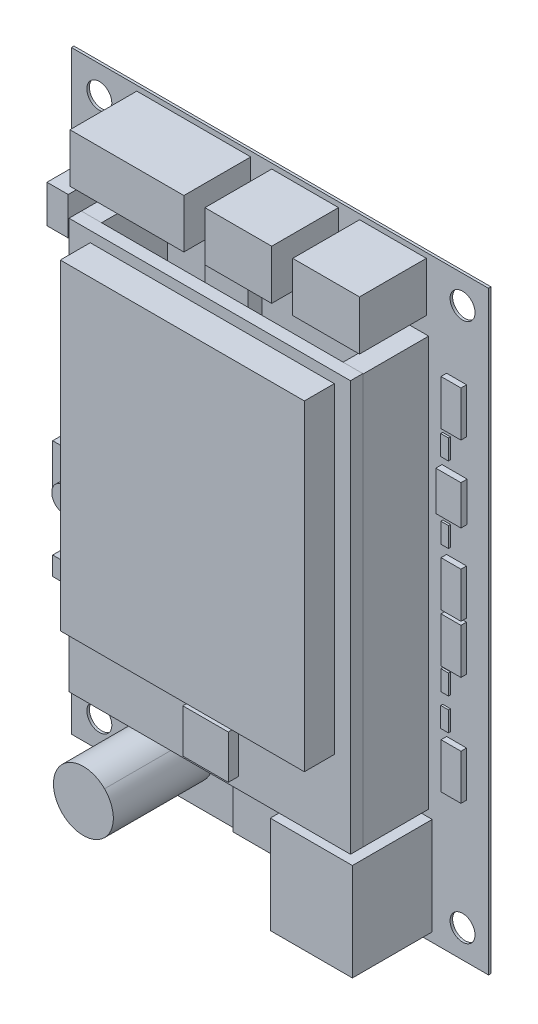
SolidWorks part; units mm, degrees
ref_plane "Front Plane" through (0, 0, 0) normal (0, 0, 1) x (1, 0, 0)
ref_plane "Top Plane" through (0, 0, 0) normal (0, 1, 0) x (1, 0, 0)
ref_plane "Right Plane" through (0, 0, 0) normal (1, 0, 0) x (0, 0, -1)
sketch "Sketch1" plane through (0, 0, 0) normal (0, 0, 1) x (1, 0, 0)
  line L0 (0, 0) -> (53.086, 0)
  line L1 (53.086, 0) -> (53.086, 75.692)
  line L2 (53.086, 75.692) -> (0, 75.692)
  line L3 (0, 75.692) -> (0, 0)
extrude "BOARD" add sketch "Sketch1" along normal blind 0.3226 separate body
ref_plane "Plane1" through (0, 0, 0.3226) normal (0, 0, 1) x (1, 0, 0)
sketch "Sketch3" plane through (0, 0, 0.3226) normal (0, 0, 1) x (1, 0, 0)
  line L0 (2.8301, 26.5189) -> (2.8301, 16.3187)
  line L1 (2.8301, 16.3187) -> (7.3299, 16.3187)
  line L2 (7.3299, 16.3187) -> (7.3299, 26.5189)
  line L3 (7.3299, 26.5189) -> (2.8301, 26.5189)
extrude "OS_SPDT-1" add sketch "Sketch3" along normal blind 3.9602 separate body
sketch "Sketch4" plane through (0, 0, 0.3226) normal (0, 0, 1) x (1, 0, 0)
  line L0 (19.6122, 6.096) -> (14.224, 11.4842)
  line L1 (14.224, 11.4842) -> (8.8358, 6.096)
  line L2 (8.8358, 6.096) -> (14.224, 0.7078)
  line L3 (14.224, 0.7078) -> (19.6122, 6.096)
extrude "SMA-50-TH-1" add sketch "Sketch4" along normal blind 12.7 separate body
sketch "Sketch5" plane through (0, 0, 0.3226) normal (0, 0, 1) x (1, 0, 0)
  line L0 (17.2989, 10.6759) -> (21.3091, 10.6759)
  line L1 (21.3091, 10.6759) -> (21.3091, 14.4031)
  line L2 (21.3091, 14.4031) -> (17.2989, 14.4031)
  line L3 (17.2989, 14.4031) -> (17.2989, 10.6759)
extrude "U_FL-1" add sketch "Sketch5" along normal blind 1.27 separate body
sketch "Sketch6" plane through (0, 0, 0.3226) normal (0, 0, 1) x (1, 0, 0)
  line L0 (33.798, 17.194) -> (23.098, 17.194)
  line L1 (23.098, 17.194) -> (23.098, 2.05)
  line L2 (23.098, 2.05) -> (33.798, 2.05)
  line L3 (33.798, 2.05) -> (33.798, 17.194)
extrude "DDPAK-1" add sketch "Sketch6" along normal blind 2.54 separate body
sketch "Sketch7" plane through (0, 0, 0.3226) normal (0, 0, 1) x (1, 0, 0)
  line L0 (24.2301, 55.4919) -> (24.2301, 62.8721)
  line L1 (24.2301, 62.8721) -> (18.7706, 62.8721)
  line L2 (18.7706, 62.8721) -> (18.7706, 55.4919)
  line L3 (18.7706, 55.4919) -> (24.2301, 55.4919)
extrude "SOIC8-1" add sketch "Sketch7" along normal blind 1.7526 separate body
sketch "Sketch8" plane through (0, 0, 0.3226) normal (0, 0, 1) x (1, 0, 0)
  line L0 (8.654, 23.876) -> (8.654, 21.336)
  line L1 (8.654, 21.336) -> (9.6241, 21.336)
  line L2 (9.6241, 21.336) -> (9.6241, 23.876)
  line L3 (9.6241, 23.876) -> (8.654, 23.876)
extrude "0603-R-1" add sketch "Sketch8" along normal blind 0.254 separate body
sketch "Sketch9" plane through (0, 0, 0.3226) normal (0, 0, 1) x (1, 0, 0)
  line L0 (47.752, 23.622) -> (47.752, 17.874)
  line L1 (47.752, 17.874) -> (50.292, 17.874)
  line L2 (50.292, 17.874) -> (50.292, 23.622)
  line L3 (50.292, 23.622) -> (47.752, 23.622)
extrude "0805_POL-1" add sketch "Sketch9" along normal blind 0.7112 separate body
sketch "Sketch10" plane through (0, 0, 0.3226) normal (0, 0, 1) x (1, 0, 0)
  line L0 (47.262, 26.924) -> (47.262, 24.384)
  line L1 (47.262, 24.384) -> (48.2321, 24.384)
  line L2 (48.2321, 24.384) -> (48.2321, 26.924)
  line L3 (48.2321, 26.924) -> (47.262, 26.924)
extrude "0603-R-2" add sketch "Sketch10" along normal blind 0.254 separate body
sketch "Sketch11" plane through (0, 0, 0.3226) normal (0, 0, 1) x (1, 0, 0)
  line L0 (48.242, 28.448) -> (48.242, 30.988)
  line L1 (48.242, 30.988) -> (47.2719, 30.988)
  line L2 (47.2719, 30.988) -> (47.2719, 28.448)
  line L3 (47.2719, 28.448) -> (48.242, 28.448)
extrude "0603-R-3" add sketch "Sketch11" along normal blind 0.254 separate body
sketch "Sketch12" plane through (0, 0, 0.3226) normal (0, 0, 1) x (1, 0, 0)
  line L0 (50.292, 31.75) -> (50.292, 37.498)
  line L1 (50.292, 37.498) -> (47.752, 37.498)
  line L2 (47.752, 37.498) -> (47.752, 31.75)
  line L3 (47.752, 31.75) -> (50.292, 31.75)
extrude "0805_POL-2" add sketch "Sketch12" along normal blind 0.7112 separate body
sketch "Sketch13" plane through (0, 0, 0.3226) normal (0, 0, 1) x (1, 0, 0)
  line L0 (30.48, 20.556) -> (27.94, 20.556)
  line L1 (27.94, 20.556) -> (27.94, 19.5859)
  line L2 (27.94, 19.5859) -> (30.48, 19.5859)
  line L3 (30.48, 19.5859) -> (30.48, 20.556)
extrude "0603-R-4" add sketch "Sketch13" along normal blind 0.254 separate body
sketch "Sketch14" plane through (0, 0, 0.3226) normal (0, 0, 1) x (1, 0, 0)
  line L0 (50.3679, 48.2999) -> (50.3679, 53.3001)
  line L1 (50.3679, 53.3001) -> (47.1681, 53.3001)
  line L2 (47.1681, 53.3001) -> (47.1681, 48.2999)
  line L3 (47.1681, 48.2999) -> (50.3679, 48.2999)
extrude "SOT505-2-1" add sketch "Sketch14" along normal blind 0.7879 separate body
sketch "Sketch15" plane through (0, 0, 0.3226) normal (0, 0, 1) x (1, 0, 0)
  line L0 (32.7025, 22.987) -> (27.7495, 22.987)
  line L1 (27.7495, 22.987) -> (27.7495, 21.209)
  line L2 (27.7495, 21.209) -> (32.7025, 21.209)
  line L3 (32.7025, 21.209) -> (32.7025, 22.987)
extrude "1206-R-1" add sketch "Sketch15" along normal blind 0.635 separate body
sketch "Sketch16" plane through (0, 0, 0.3226) normal (0, 0, 1) x (1, 0, 0)
  line L0 (16.238, 16.764) -> (16.238, 19.304)
  line L1 (16.238, 19.304) -> (15.2679, 19.304)
  line L2 (15.2679, 19.304) -> (15.2679, 16.764)
  line L3 (15.2679, 16.764) -> (16.238, 16.764)
extrude "0603-R-5" add sketch "Sketch16" along normal blind 0.254 separate body
sketch "Sketch17" plane through (0, 0, 0.3226) normal (0, 0, 1) x (1, 0, 0)
  line L0 (26.416, 18.052) -> (28.956, 18.052)
  line L1 (28.956, 18.052) -> (28.956, 19.0221)
  line L2 (28.956, 19.0221) -> (26.416, 19.0221)
  line L3 (26.416, 19.0221) -> (26.416, 18.052)
extrude "0603-R-6" add sketch "Sketch17" along normal blind 0.254 separate body
sketch "Sketch18" plane through (0, 0, 0.3226) normal (0, 0, 1) x (1, 0, 0)
  line L0 (47.262, 56.896) -> (47.262, 54.356)
  line L1 (47.262, 54.356) -> (48.2321, 54.356)
  line L2 (48.2321, 54.356) -> (48.2321, 56.896)
  line L3 (48.2321, 56.896) -> (47.262, 56.896)
extrude "0603-R-7" add sketch "Sketch18" along normal blind 0.254 separate body
sketch "Sketch19" plane through (0, 0, 0.3226) normal (0, 0, 1) x (1, 0, 0)
  line L0 (48.242, 44.704) -> (48.242, 47.244)
  line L1 (48.242, 47.244) -> (47.2719, 47.244)
  line L2 (47.2719, 47.244) -> (47.2719, 44.704)
  line L3 (47.2719, 44.704) -> (48.242, 44.704)
extrude "0603-R-8" add sketch "Sketch19" along normal blind 0.254 separate body
sketch "Sketch20" plane through (0, 0, 0.3226) normal (0, 0, 1) x (1, 0, 0)
  line L0 (24.0665, 54.229) -> (19.1135, 54.229)
  line L1 (19.1135, 54.229) -> (19.1135, 52.451)
  line L2 (19.1135, 52.451) -> (24.0665, 52.451)
  line L3 (24.0665, 52.451) -> (24.0665, 54.229)
extrude "1206-R-2" add sketch "Sketch20" along normal blind 0.635 separate body
sketch "Sketch21" plane through (0, 0, 0.3226) normal (0, 0, 1) x (1, 0, 0)
  line L0 (47.752, 43.688) -> (47.752, 37.94)
  line L1 (47.752, 37.94) -> (50.292, 37.94)
  line L2 (50.292, 37.94) -> (50.292, 43.688)
  line L3 (50.292, 43.688) -> (47.752, 43.688)
extrude "0805_POL-3" add sketch "Sketch21" along normal blind 0.7112 separate body
sketch "Sketch22" plane through (0, 0, 0.3226) normal (0, 0, 1) x (1, 0, 0)
  line L0 (50.292, 57.912) -> (50.292, 63.66)
  line L1 (50.292, 63.66) -> (47.752, 63.66)
  line L2 (47.752, 63.66) -> (47.752, 57.912)
  line L3 (47.752, 57.912) -> (50.292, 57.912)
extrude "0805_POL-4" add sketch "Sketch22" along normal blind 0.7112 separate body
sketch "Sketch23" plane through (0, 0, 0.3226) normal (0, 0, 1) x (1, 0, 0)
  line L0 (9.634, 16.764) -> (9.634, 19.304)
  line L1 (9.634, 19.304) -> (8.6639, 19.304)
  line L2 (8.6639, 19.304) -> (8.6639, 16.764)
  line L3 (8.6639, 16.764) -> (9.634, 16.764)
extrude "0603-R-9" add sketch "Sketch23" along normal blind 0.254 separate body
sketch "Sketch24" plane through (0, 0, 0.3226) normal (0, 0, 1) x (1, 0, 0)
  line L0 (3.302, 12.446) -> (3.302, 6.698)
  line L1 (3.302, 6.698) -> (5.842, 6.698)
  line L2 (5.842, 6.698) -> (5.842, 12.446)
  line L3 (5.842, 12.446) -> (3.302, 12.446)
extrude "0805_POL-5" add sketch "Sketch24" along normal blind 0.7112 separate body
sketch "Sketch25" plane through (0, 0, 0.3226) normal (0, 0, 1) x (1, 0, 0)
  line L0 (22.8239, 75.04) -> (8.3241, 75.04)
  line L1 (8.3241, 75.04) -> (8.3241, 68.8114)
  line L2 (8.3241, 68.8114) -> (22.8239, 68.8114)
  line L3 (22.8239, 68.8114) -> (22.8239, 75.04)
extrude "HDR_SHERLOCK_6P_V-1" add sketch "Sketch25" along normal blind 8.509 separate body
sketch "Sketch26" plane through (0, 0, 0.3226) normal (0, 0, 1) x (1, 0, 0)
  line L0 (33.9999, 75.04) -> (25.5001, 75.04)
  line L1 (25.5001, 75.04) -> (25.5001, 68.736)
  line L2 (25.5001, 68.736) -> (33.9999, 68.736)
  line L3 (33.9999, 68.736) -> (33.9999, 75.04)
extrude "HDR_SHERLOCK_3P_V-1" add sketch "Sketch26" along normal blind 8.509 separate body
sketch "Sketch27" plane through (0, 0, 0.3226) normal (0, 0, 1) x (1, 0, 0)
  line L0 (45.1759, 75.04) -> (36.6761, 75.04)
  line L1 (36.6761, 75.04) -> (36.6761, 68.736)
  line L2 (36.6761, 68.736) -> (45.1759, 68.736)
  line L3 (45.1759, 68.736) -> (45.1759, 75.04)
extrude "HDR_SHERLOCK_3P_V-2" add sketch "Sketch27" along normal blind 8.509 separate body
sketch "Sketch28" plane through (0, 0, 0) normal (0, 0, 1) x (1, 0, 0)
  line L0 (42.7479, 67.6181) -> (39.194, 67.6181)
  line L1 (39.194, 67.6181) -> (39.194, 70.5165)
  line L2 (39.194, 70.5165) -> (42.7479, 70.5165)
  line L3 (42.7479, 70.5165) -> (42.7479, 67.6181)
extrude "SOT-23-1" add sketch "Sketch28" against normal blind 1.0922 separate body
sketch "Sketch29" plane through (0, 0, 0) normal (0, 0, 1) x (1, 0, 0)
  line L0 (31.5719, 67.6181) -> (28.018, 67.6181)
  line L1 (28.018, 67.6181) -> (28.018, 70.5165)
  line L2 (28.018, 70.5165) -> (31.5719, 70.5165)
  line L3 (31.5719, 70.5165) -> (31.5719, 67.6181)
extrude "SOT-23-2" add sketch "Sketch29" against normal blind 1.0922 separate body
sketch "Sketch30" plane through (0, 0, 0.3226) normal (0, 0, 1) x (1, 0, 0)
  line L0 (9.1948, 34.7116) -> (1.1707, 34.7116)
  line L1 (1.1707, 34.7116) -> (1.1707, 28.5118)
  line L2 (1.1707, 28.5118) -> (9.1948, 28.5118)
  line L3 (9.1948, 28.5118) -> (9.1948, 34.7116)
extrude "SPST_6MM-1" add sketch "Sketch30" along normal blind 3.556 separate body
sketch "Sketch31" plane through (0, 0, 0.3226) normal (0, 0, 1) x (1, 0, 0)
  line L0 (18.796, 64.026) -> (21.336, 64.026)
  line L1 (21.336, 64.026) -> (21.336, 64.9961)
  line L2 (21.336, 64.9961) -> (18.796, 64.9961)
  line L3 (18.796, 64.9961) -> (18.796, 64.026)
extrude "0603-R-10" add sketch "Sketch31" along normal blind 0.254 separate body
sketch "Sketch32" plane through (0, 0, 0.3226) normal (0, 0, 1) x (1, 0, 0)
  line L0 (24.384, 65.006) -> (21.844, 65.006)
  line L1 (21.844, 65.006) -> (21.844, 64.0359)
  line L2 (21.844, 64.0359) -> (24.384, 64.0359)
  line L3 (24.384, 64.0359) -> (24.384, 65.006)
extrude "0603-R-11" add sketch "Sketch32" along normal blind 0.254 separate body
sketch "Sketch33" plane through (0, 0, 0.3226) normal (0, 0, 1) x (1, 0, 0)
  line L0 (39.751, 54.2925) -> (39.751, 49.3395)
  line L1 (39.751, 49.3395) -> (41.529, 49.3395)
  line L2 (41.529, 49.3395) -> (41.529, 54.2925)
  line L3 (41.529, 54.2925) -> (39.751, 54.2925)
extrude "1206-R-3" add sketch "Sketch33" along normal blind 0.635 separate body
sketch "Sketch34" plane through (0, 0, 0) normal (0, 0, 1) x (1, 0, 0)
  line L0 (13.0884, 70.5104) -> (13.0884, 67.9704)
  line L1 (13.0884, 67.9704) -> (12.1183, 67.9704)
  line L2 (12.1183, 67.9704) -> (12.1183, 70.5104)
  line L3 (12.1183, 70.5104) -> (13.0884, 70.5104)
extrude "0603-R-12" add sketch "Sketch34" against normal blind 0.254 separate body
sketch "Sketch35" plane through (0, 0, 0) normal (0, 0, 1) x (1, 0, 0)
  line L0 (19.0828, 70.5104) -> (19.0828, 67.9704)
  line L1 (19.0828, 67.9704) -> (18.1127, 67.9704)
  line L2 (18.1127, 67.9704) -> (18.1127, 70.5104)
  line L3 (18.1127, 70.5104) -> (19.0828, 70.5104)
extrude "0603-R-13" add sketch "Sketch35" against normal blind 0.254 separate body
sketch "Sketch36" plane through (0, 0, 0) normal (0, 0, 1) x (1, 0, 0)
  line L0 (15.0696, 70.5104) -> (15.0696, 67.9704)
  line L1 (15.0696, 67.9704) -> (14.0995, 67.9704)
  line L2 (14.0995, 67.9704) -> (14.0995, 70.5104)
  line L3 (14.0995, 70.5104) -> (15.0696, 70.5104)
extrude "0603-R-14" add sketch "Sketch36" against normal blind 0.254 separate body
sketch "Sketch37" plane through (0, 0, 0) normal (0, 0, 1) x (1, 0, 0)
  line L0 (17.0508, 70.5104) -> (17.0508, 67.9704)
  line L1 (17.0508, 67.9704) -> (16.0807, 67.9704)
  line L2 (16.0807, 67.9704) -> (16.0807, 70.5104)
  line L3 (16.0807, 70.5104) -> (17.0508, 70.5104)
extrude "0603-R-15" add sketch "Sketch37" against normal blind 0.254 separate body
sketch "Sketch38" plane through (0, 0, 0.3226) normal (0, 0, 1) x (1, 0, 0)
  line L0 (8.4836, 63.3745) -> (8.4836, 68.1721)
  line L1 (8.4836, 68.1721) -> (5.78, 68.1721)
  line L2 (5.78, 68.1721) -> (5.78, 63.3745)
  line L3 (5.78, 63.3745) -> (8.4836, 63.3745)
extrude "HDR_2P1R_100MIL-1" add sketch "Sketch38" along normal blind 8.89 separate body
sketch "Sketch39" plane through (0, 0, 0.3226) normal (0, 0, 1) x (1, 0, 0)
  line L0 (35.4691, 13.5659) -> (35.4691, 1.1661)
  line L1 (35.4691, 1.1661) -> (45.9229, 1.1661)
  line L2 (45.9229, 1.1661) -> (45.9229, 13.5659)
  line L3 (45.9229, 13.5659) -> (35.4691, 13.5659)
extrude "HDR_MFITJR_2R2P-V-1" add sketch "Sketch39" along normal blind 10.16 separate body
sketch "Sketch40" plane through (0, 0, 0.3226) normal (0, 0, 1) x (1, 0, 0)
  line L0 (39.8838, 12.9741) -> (39.8838, 22.5509)
  line L1 (39.8838, 22.5509) -> (34.1841, 22.5509)
  line L2 (34.1841, 22.5509) -> (34.1841, 12.9741)
  line L3 (34.1841, 12.9741) -> (39.8838, 12.9741)
extrude "SMC-R-1" add sketch "Sketch40" along normal blind 2.5146 separate body
hole_wizard "1/8 (0.125) Diameter Hole1" positions "3DSketch1" profile "Sketch45" hole size "1/8" standard "Ansi Inch"
sketch3d "3DSketch1"
  point P0 (3.556, 3.556, 0.3226)
  point P2 (49.784, 3.556, 0.3226)
  point P4 (3.556, 72.136, 0.3226)
  point P6 (49.784, 72.136, 0.3226)
sketch "Sketch45" plane through (3.556, 3.556, 0.3226) normal (1, 0, 0) x (0, -1, 0)
  line L0 (0, 0) -> (0, 26.3539)
  line L1 (0, 26.3539) -> (1.5875, 25.4)
  line L2 (1.5875, 25.4) -> (1.5875, 0)
  line L5 (1.5875, 0) -> (0, 0)
  line L10 (0, 26.3539) -> (-1.5875, 25.4) construction
  line L11 (0, -6.35) -> (0, 107.95) construction
  dimension "Hole Dia." = 3.175
  dimension "Hole Depth" = 25.4
  dimension "Drill Angle" = 118
fillet "Fillet2" radius 3.81 1 edges at (14.224, 0.7078, 6.6726)
fillet "Fillet3" radius 3.81 3 edges at (8.8358, 6.096, 6.6726) (14.224, 11.4842, 6.6726) (19.6122, 6.096, 6.6726)
ref_plane "Plane2" through (45.847, 66.675, 15.5853) normal (-1, 0, 0) x (0, 0, 1)
sketch "Sketch51" plane through (0, 0, 0.3226) normal (0, 0, 1) x (1, 0, 0)
  line L1 (9.652, 66.675) -> (12.2223, 66.675)
  line L2 (9.652, 66.675) -> (9.652, 14.5339)
  line L3 (9.652, 14.5339) -> (12.2223, 14.5339)
  line L4 (12.2223, 66.675) -> (12.2223, 14.5339)
extrude "Extrude42" add sketch "Sketch51" along normal blind 8.382
sketch "Sketch53" plane through (33.0593, 4.01, 0.3226) normal (0, 0, 1) x (1, 0, 0)
  line L1 (9.8441, 62.6045) -> (12.4143, 62.6045)
  line L2 (9.8441, 62.6045) -> (9.8441, 10.4634)
  line L3 (9.8441, 10.4634) -> (12.4143, 10.4634)
  line L4 (12.4143, 62.6045) -> (12.4143, 10.4634)
extrude "Extrude43" add sketch "Sketch53" along normal blind 8.382
sketch "Sketch54" plane through (0, 0, 3.8786) normal (0, 0, 1) x (1, 0, 0)
  circle A0 centre (5.1891, 31.4939) radius 1.5966
extrude "Extrude44" add sketch "Sketch54" along normal blind 2.54
sketch "Sketch55" plane through (0, 0, 4.2828) normal (0, 0, 1) x (1, 0, 0)
  line L1 (4.1205, 25.0599) -> (6.312, 25.0599)
  line L2 (4.1205, 25.0599) -> (4.1205, 22.6834)
  line L3 (4.1205, 22.6834) -> (6.312, 22.6834)
  line L4 (6.312, 25.0599) -> (6.312, 22.6834)
extrude "Extrude45" add sketch "Sketch55" along normal blind 2.54
sketch "Sketch56" plane through (0, 0, 8.7046) normal (0, 0, 1) x (1, 0, 0)
  line L1 (9.652, 66.675) -> (45.4736, 66.675)
  line L2 (9.652, 66.675) -> (9.652, 14.4734)
  line L3 (9.652, 14.4734) -> (45.4736, 14.4734)
  line L4 (45.4736, 66.675) -> (45.4736, 14.4734)
extrude "Extrude47" add sketch "Sketch56" along normal blind 1.5748 separate body
sketch "Sketch58" plane through (0, 0, 10.2794) normal (0, 0, 1) x (1, 0, 0)
  line L1 (12.3552, 65.3248) -> (43.417, 65.3248)
  line L2 (12.3552, 65.3248) -> (12.3552, 24.4482)
  line L3 (12.3552, 24.4482) -> (43.417, 24.4482)
  line L4 (43.417, 65.3248) -> (43.417, 24.4482)
extrude "Extrude48" add sketch "Sketch58" along normal blind 3.81
sketch "Sketch59" plane through (0, 0, 10.2794) normal (0, 0, 1) x (1, 0, 0)
  line L1 (25.4078, 21.4479) -> (31.1999, 21.4479)
  line L2 (25.4078, 21.4479) -> (25.4078, 15.9045)
  line L3 (25.4078, 15.9045) -> (31.1999, 15.9045)
  line L4 (31.1999, 21.4479) -> (31.1999, 15.9045)
extrude "Extrude49" add sketch "Sketch59" along normal blind 1.27
